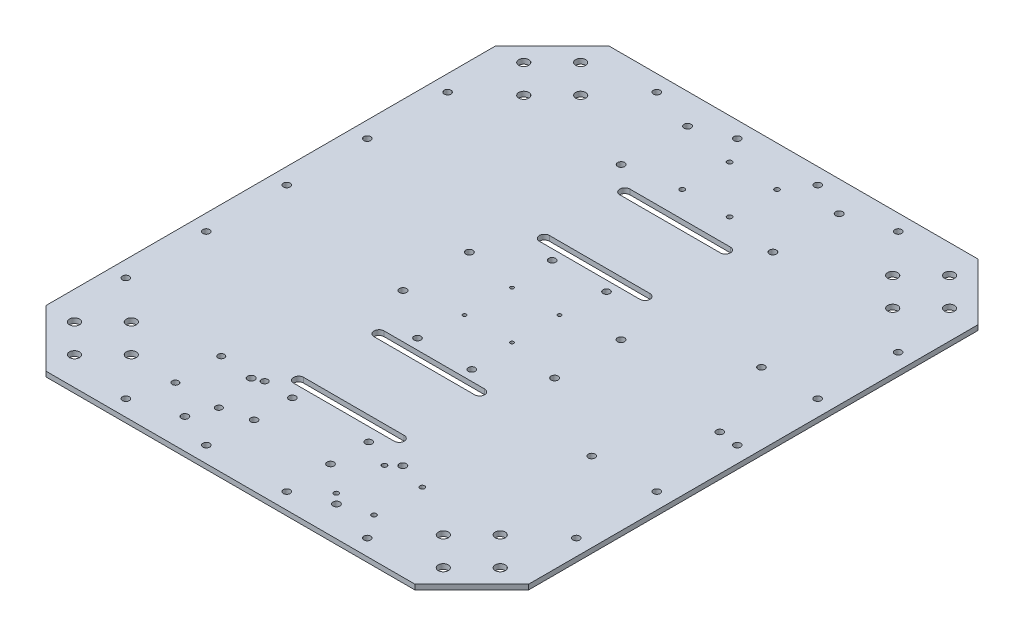
SolidWorks part; units mm, degrees
ref_plane "Front Plane" through (0, 0, 0) normal (0, 0, 1) x (1, 0, 0)
ref_plane "Top Plane" through (0, 0, 0) normal (0, 1, 0) x (1, 0, 0)
ref_plane "Right Plane" through (0, 0, 0) normal (1, 0, 0) x (0, 0, -1)
sketch "Sketch1" plane through (0, 0, 0) normal (0, 1, 0) x (1, 0, 0)
  line L0 (-121.2861, 87.138) -> (-85.365, 123.059)
  line L1 (-121.2861, 123.059) -> (183.5139, 123.059)
  line L2 (-121.2861, 123.059) -> (-121.2861, -232.541)
  line L3 (-121.2861, -232.541) -> (183.5139, -232.541)
  line L4 (183.5139, 123.059) -> (183.5139, -232.541)
  line L5 (31.1139, 95.069) -> (31.1139, -294.9418) construction
  line L6 (-146.0448, -54.741) -> (218.038, -54.741) construction
  line L7 (183.5139, 87.138) -> (147.5929, 123.059)
  line L8 (183.5139, -196.62) -> (147.5929, -232.541)
  line L9 (-121.2861, -196.62) -> (-85.365, -232.541)
  circle A0 centre (-16.7651, 104.009) radius 2.2225
  circle A1 centre (78.9929, 104.009) radius 2.2225
  circle A2 centre (-16.7651, 62.099) radius 2.2225
  circle A3 centre (78.9929, 62.099) radius 2.2225
  circle A4 centre (-16.7651, -171.581) radius 2.2225
  circle A5 centre (78.9929, -171.581) radius 2.2225
  circle A6 centre (78.9929, -213.491) radius 2.2225
  circle A7 centre (-16.7651, -213.491) radius 2.2225
  circle A8 centre (-16.7651, -33.786) radius 2.2225
  circle A9 centre (78.9929, -33.786) radius 2.2225
  circle A10 centre (78.9929, -75.696) radius 2.2225
  circle A11 centre (-16.7651, -75.696) radius 2.2225
  point P8 (31.1139, 123.059)
  point P11 (-121.2861, -54.741)
  dimension "D6" = 95.758
  dimension "D13" = 4.445
  dimension "D1" = 304.8
  dimension "D2" = 355.6
  dimension "D3" = 45
  dimension "D4" = 50.8
  dimension "D5" = 41.91
  dimension "D7" = 104.521
  dimension "D8" = 19.05
  dimension "D9" = 41.91
  dimension "D10" = 20.955
  dimension "D11" = 95.758
  dimension "D12" = 47.879
extrude "Boss-Extrude1" add sketch "Sketch1" along normal blind 3.175 contours L2 L9 L3 L8 L4 L7 L1 L0 region at (31.1139, 0, 54.741)
sketch "Sketch2" plane through (0, 3.175, 0) normal (0, 1, 0) x (1, 0, 0)
  line L0 (31.1139, 123.059) -> (31.1139, -287.8465) construction
  line L1 (-85.365, 123.059) -> (147.5929, 123.059) construction
  line L2 (183.5139, -54.741) -> (-158.2106, -54.741) construction
  line L3 (183.5139, 87.138) -> (183.5139, -196.62) construction
  circle A0 centre (13.8419, -12.069) radius 2.159
  circle A1 centre (48.1319, -12.069) radius 2.159
  circle A2 centre (13.8419, -97.159) radius 2.159
  circle A3 centre (48.1319, -97.159) radius 2.159
  dimension "D5" = 4.318
  dimension "D6" = 4.318
  dimension "D7" = 4.318
  dimension "D8" = 4.318
  dimension "D1" = 17.272
  dimension "D2" = 34.29
  dimension "D3" = 85.09
  dimension "D4" = 42.672
extrude "Cut-Extrude1" cut sketch "Sketch2" against normal through all
sketch "Sketch4" plane through (0, 3.175, 0) normal (0, 1, 0) x (1, 0, 0)
  line L0 (-0.6361, 48.256) -> (62.8639, 48.256) construction
  line L1 (-0.6361, 51.431) -> (62.8639, 51.431)
  line L2 (-0.6361, 45.081) -> (62.8639, 45.081)
  line L3 (-0.6361, -2.544) -> (62.8639, -2.544) construction
  line L4 (-0.6361, 0.631) -> (62.8639, 0.631)
  line L5 (-0.6361, -5.719) -> (62.8639, -5.719)
  line L6 (31.1139, 123.059) -> (31.1139, -75.2432) construction
  line L7 (-85.365, 123.059) -> (147.5929, 123.059) construction
  line L8 (-121.2861, -54.741) -> (257.7387, -54.741) construction
  line L9 (-121.2861, 87.138) -> (-121.2861, -196.62) construction
  line L10 (31.1139, -232.541) -> (31.1139, -34.2388) construction
  line L11 (-0.6361, -106.938) -> (62.8639, -106.938) construction
  line L12 (-0.6361, -110.113) -> (62.8639, -110.113)
  line L13 (-0.6361, -103.763) -> (62.8639, -103.763)
  line L14 (-0.6361, -157.738) -> (62.8639, -157.738) construction
  line L15 (-0.6361, -160.913) -> (62.8639, -160.913)
  line L16 (-0.6361, -154.563) -> (62.8639, -154.563)
  arc A0 (-0.6361, 51.431) -> (-0.6361, 45.081) centre (-0.6361, 48.256) ccw
  arc A1 (62.8639, 45.081) -> (62.8639, 51.431) centre (62.8639, 48.256) ccw
  arc A2 (-0.6361, 0.631) -> (-0.6361, -5.719) centre (-0.6361, -2.544) ccw
  arc A3 (62.8639, -5.719) -> (62.8639, 0.631) centre (62.8639, -2.544) ccw
  circle A4 centre (48.1319, -12.069) radius 2.159 construction
  arc A5 (-0.6361, -110.113) -> (-0.6361, -103.763) centre (-0.6361, -106.938) cw
  arc A6 (62.8639, -103.763) -> (62.8639, -110.113) centre (62.8639, -106.938) cw
  arc A7 (-0.6361, -160.913) -> (-0.6361, -154.563) centre (-0.6361, -157.738) cw
  arc A8 (62.8639, -154.563) -> (62.8639, -160.913) centre (62.8639, -157.738) cw
  point P2 (31.1139, 48.256)
  point P7 (31.1139, -2.544)
  point P28 (31.1139, -106.938)
  point P35 (31.1139, -157.738)
  dimension "D1" = 63.5
  dimension "D2" = 63.5
  dimension "D3" = 6.35
  dimension "D4" = 6.35
  dimension "D5" = 44.45
  dimension "D6" = 6.35
extrude "Cut-Extrude2" cut sketch "Sketch4" against normal through all
sketch "Sketch7" plane through (0, 3.175, 0) normal (0, 1, 0) x (1, 0, 0)
  line L0 (31.1139, 123.059) -> (31.1139, -19.2461) construction
  line L3 (-85.365, 123.059) -> (147.5929, 123.059) construction
  circle A0 centre (16.1279, 67.687) radius 1.524
  circle A1 centre (46.0999, 67.687) radius 1.524
  circle A2 centre (16.1279, 97.659) radius 1.524
  circle A3 centre (46.0999, 97.659) radius 1.524
  dimension "D1" = 3.048
  dimension "D2" = 3.048
  dimension "D4" = 14.986
  dimension "D3" = 29.972
  dimension "D5" = 25.4
extrude "Cut-Extrude3" cut sketch "Sketch7" against normal through all
sketch "Sketch8" plane through (0, 3.175, 0) normal (0, 1, 0) x (1, 0, 0)
  line L0 (-85.365, -232.541) -> (147.5929, -232.541) construction
  line L1 (183.5139, 87.138) -> (183.5139, -196.62) construction
  circle A0 centre (73.0239, -207.649) radius 1.524
  circle A1 centre (73.0239, -177.169) radius 1.524
  circle A2 centre (96.8999, -207.649) radius 1.524
  circle A3 centre (96.8999, -177.169) radius 1.524
  dimension "D1" = 3.048
  dimension "D2" = 30.48
  dimension "D3" = 23.876
  dimension "D4" = 24.892
  dimension "D5" = 86.614
extrude "Cut-Extrude4" cut sketch "Sketch8" against normal through all and the other way through all
sketch "Sketch10" plane through (0, 0, 0) normal (0, -1, 0) x (1, 0, 0)
  line L0 (-85.365, 232.541) -> (147.5929, 232.541) construction
  line L1 (31.1139, 232.541) -> (31.1139, 128.7119) construction
  circle A0 centre (6.9839, 193.4758) radius 2.159
  circle A1 centre (55.2439, 193.4758) radius 2.159
  circle A2 centre (6.9839, 169.3458) radius 2.159
  circle A3 centre (55.2439, 169.3458) radius 2.159
  dimension "D1" = 4.318
  dimension "D2" = 48.26
  dimension "D4" = 39.0652
  dimension "D6" = 4.318
  dimension "D7" = 4.318
  dimension "D8" = 4.318
  dimension "D3" = 24.13
  dimension "D5" = 24.13
extrude "Cut-Extrude6" cut sketch "Sketch10" against normal through all
sketch "Sketch9" plane through (0, 0, 0) normal (0, -1, 0) x (-1, 0, 0)
  line L0 (85.365, -232.541) -> (-147.5929, -232.541) construction
  line L1 (121.2861, 87.138) -> (121.2861, -196.62) construction
  circle A0 centre (38.2281, -197.9691) radius 2.032
  circle A1 centre (10.7961, -197.9691) radius 2.032
  circle A2 centre (38.2281, -169.0131) radius 2.032
  circle A3 centre (10.7961, -169.0131) radius 2.032
  dimension "D1" = 4.064
  dimension "D2" = 27.432
  dimension "D3" = 28.956
  dimension "D4" = 34.5719
  dimension "D5" = 83.058
extrude "Cut-Extrude5" cut sketch "Sketch9" against normal through all
sketch "Sketch13" plane through (0, 0, 0) normal (0, -1, 0) x (1, 0, 0)
  line L0 (31.1139, -123.059) -> (31.1139, 261.4711) construction
  line L1 (-85.365, -123.059) -> (147.5929, -123.059) construction
  line L2 (-121.2861, 54.741) -> (239.2508, 54.741) construction
  line L3 (-121.2861, -87.138) -> (-121.2861, 196.62) construction
  circle A0 centre (16.1139, 69.741) radius 1.1
  circle A1 centre (16.1139, 39.741) radius 1.1
  circle A2 centre (46.1139, 39.741) radius 1.1
  circle A3 centre (46.1139, 69.741) radius 1.1
  dimension "D1" = 2.2
  dimension "D2" = 2.2
  dimension "D3" = 30
  dimension "D4" = 15
  dimension "D5" = 15
extrude "Cut-Extrude8" cut sketch "Sketch13" against normal through all
sketch "Sketch14" plane through (0, 0, 0) normal (0, -1, 0) x (1, 0, 0)
  line L0 (31.1139, 232.541) -> (31.1139, -154.5354) construction
  line L1 (-85.365, 232.541) -> (147.5929, 232.541) construction
  line L2 (-121.2861, 54.741) -> (331.9066, 54.741) construction
  line L3 (-121.2861, -87.138) -> (-121.2861, 196.62) construction
  line L4 (-85.365, 214.5805) -> (-103.3255, 196.62) construction
  line L5 (-103.3255, 196.62) -> (-85.365, 178.6595) construction
  line L6 (-85.365, 178.6595) -> (-67.4045, 196.62) construction
  line L7 (-67.4045, 196.62) -> (-85.365, 214.5805) construction
  line L8 (-121.2861, 196.62) -> (-85.365, 232.541) construction
  line L9 (-103.3255, 214.5805) -> (-48.3665, 159.6215) construction
  circle A0 centre (-103.3255, 196.62) radius 3.175
  circle A1 centre (-85.365, 214.5805) radius 3.175
  circle A2 centre (-85.365, 178.6595) radius 3.175
  circle A3 centre (-67.4045, 196.62) radius 3.175
  circle A4 centre (129.6324, 196.62) radius 3.175
  circle A5 centre (147.5929, 178.6595) radius 3.175
  circle A6 centre (165.5534, 196.62) radius 3.175
  circle A7 centre (147.5929, 214.5805) radius 3.175
  circle A8 centre (-85.365, -105.0985) radius 3.175
  circle A9 centre (-103.3255, -87.138) radius 3.175
  circle A10 centre (-85.365, -69.1774) radius 3.175
  circle A11 centre (-67.4045, -87.138) radius 3.175
  circle A12 centre (165.5534, -87.138) radius 3.175
  circle A13 centre (147.5929, -69.1774) radius 3.175
  circle A14 centre (147.5929, -105.0985) radius 3.175
  circle A15 centre (129.6324, -87.138) radius 3.175
  dimension "D3" = 6.35
  dimension "D4" = 6.35
  dimension "D5" = 6.35
  dimension "D6" = 6.35
  dimension "D2" = 12.7
  dimension "D7" = 90
  dimension "D8" = 25.4
  dimension "D9" = 25.4
  dimension "D10" = 12.7
  dimension "D11" = 90
extrude "Cut-Extrude9" cut sketch "Sketch14" against normal through all
sketch "Sketch15" plane through (0, 0, 0) normal (0, -1, 0) x (1, 0, 0)
  line L0 (31.1139, 232.541) -> (31.1139, 125.875) construction
  line L1 (-85.365, 232.541) -> (147.5929, 232.541) construction
  line L2 (-121.2861, 54.741) -> (75.4631, 54.741) construction
  line L3 (-121.2861, -87.138) -> (-121.2861, 196.62) construction
  circle A0 centre (5.7139, 222.381) radius 2.159
  circle A1 centre (-45.0861, 222.381) radius 2.159
  circle A2 centre (-111.1261, 54.741) radius 2.159
  circle A3 centre (-111.1261, 105.541) radius 2.159
  circle A4 centre (-111.1261, 156.341) radius 2.159
  circle A5 centre (173.3539, 156.341) radius 2.159
  circle A6 centre (173.3539, 105.541) radius 2.159
  circle A7 centre (173.3539, 54.741) radius 2.159
  circle A8 centre (107.3139, 222.381) radius 2.159
  circle A9 centre (56.5139, 222.381) radius 2.159
  circle A10 centre (56.5139, -112.899) radius 2.159
  circle A11 centre (107.3139, -112.899) radius 2.159
  circle A12 centre (173.3539, 3.941) radius 2.159
  circle A13 centre (173.3539, -46.859) radius 2.159
  circle A14 centre (-111.1261, -46.859) radius 2.159
  circle A15 centre (-111.1261, 3.941) radius 2.159
  circle A16 centre (-45.0861, -112.899) radius 2.159
  circle A17 centre (5.7139, -112.899) radius 2.159
  dimension "D3" = 4.318
  dimension "D4" = 4.318
  dimension "D8" = 4.318
  dimension "D9" = 4.318
  dimension "D10" = 4.318
  dimension "D1" = 25.4
  dimension "D2" = 50.8
  dimension "D5" = 10.16
  dimension "D6" = 50.8
  dimension "D7" = 50.8
  dimension "D11" = 10.16
extrude "Cut-Extrude10" cut sketch "Sketch15" against normal through all
sketch "Sketch16" plane through (0, 0, 0) normal (0, -1, 0) x (-1, 0, 0)
  line L1 (-103.7737, -99.6794) -> (-153.6537, -99.6794)
  line L2 (-103.7737, -99.6794) -> (-103.7737, -11.5294)
  line L3 (-103.7737, -11.5294) -> (-153.6537, -11.5294)
  line L4 (-153.6537, -99.6794) -> (-153.6537, -11.5294)
  line L5 (-183.5139, 87.138) -> (-183.5139, -196.62) construction
  circle A0 centre (-133.3337, -106.6794) radius 2.159
  circle A1 centre (-138.4137, -4.5294) radius 2.159
  circle A2 centre (-160.6539, -53.0294) radius 2.159
  dimension "D3" = 7
  dimension "D4" = 7.0002
  dimension "D5" = 7
  dimension "D6" = 20.32
  dimension "D7" = 15.24
  dimension "D8" = 46.65
  dimension "D9" = 4.318
  dimension "D10" = 4.318
  dimension "D11" = 4.318
  dimension "D1" = 88.15
  dimension "D2" = 49.88
  dimension "D12" = 22.86
extrude "Cut-Extrude11" cut sketch "Sketch16" against normal through all contours A2 | A0 | A1
